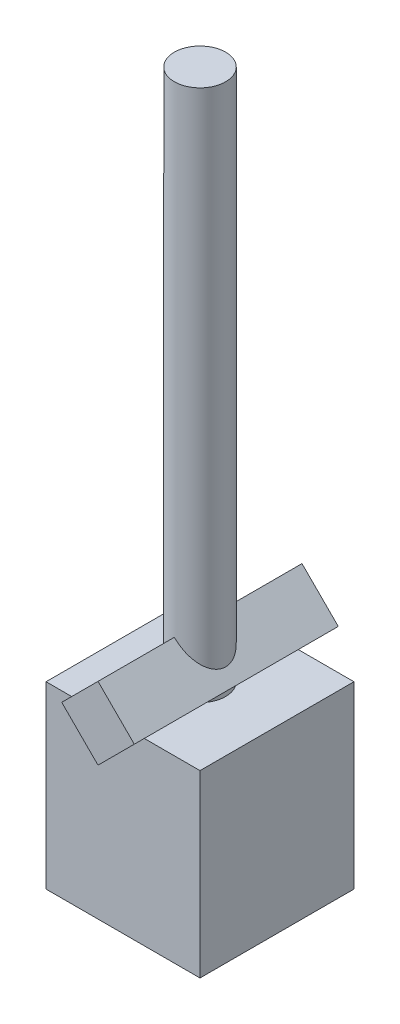
SolidWorks part; units mm, degrees
note: '?' marks a value the reader was unsure of.
material "Brass"
ref_plane "Front Plane" through (0, 0, 0) normal (0, 0, 1) x (1, 0, 0)
ref_plane "Top Plane" through (0, 0, 0) normal (0, 1, 0) x (1, 0, 0)
ref_plane "Right Plane" through (0, 0, 0) normal (1, 0, 0) x (0, 0, -1)
sketch "Sketch1" plane through (0, 0, 0) normal (0, 0, 1) x (1, 0, 0)
  line L0 (0, 0) -> (5.6569, -5.6569)
  line L1 (5.6569, -5.6569) -> (0, -11.3137)
  line L2 (0, -11.3137) -> (-5.6569, -5.6569)
  line L3 (-5.6569, -5.6569) -> (0, 0)
  dimension "D1" = 5.6569
  dimension "D2" = 5.6569
  dimension "D3" = 5.6569
  dimension "D4" = 5.6569
  dimension "D5" = 5.6569
  dimension "D6" = 5.6569
extrude "Boss-Extrude1" add sketch "Sketch1" along normal mid plane 31.8
sketch "Sketch2" plane through (0, 0, 0) normal (0, 0, 1) x (1, 0, 0)
  line L0 (-12, -36) -> (12, -36)
  line L1 (12, -36) -> (12, -8)
  line L2 (12, -8) -> (-12, -8)
  line L3 (-12, -8) -> (-12, -36)
  dimension "D1" = 24
  dimension "D2" = 28
  dimension "D3" = 12
  dimension "D4" = 36
extrude "Boss-Extrude2" add sketch "Sketch2" along normal mid plane 24
sketch "Sketch3" plane through (0, 0, 0) normal (0, 1, 0) x (1, 0, 0)
  circle A0 centre (0, 0) radius 4
  dimension "D1" = 8
extrude "Boss-Extrude3" add sketch "Sketch3" along normal blind 83 from offset 8
ref_axis "Axis1" through (0, 0, -17.49) along (0, 0, 1)?
